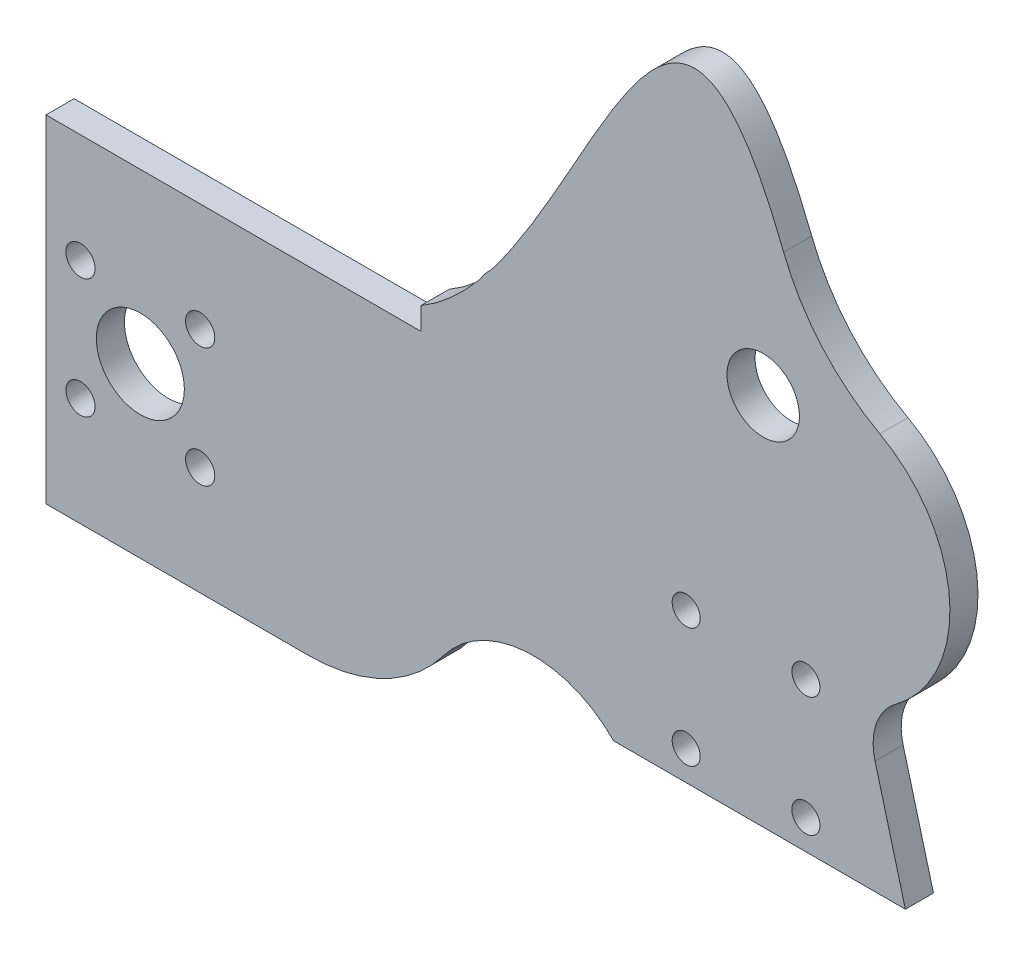
SolidWorks part; units mm, degrees
ref_plane "Front Plane" through (0, 0, 0) normal (0, 0, 1) x (1, 0, 0)
ref_plane "Top Plane" through (0, 0, 0) normal (0, 1, 0) x (1, 0, 0)
ref_plane "Right Plane" through (0, 0, 0) normal (1, 0, 0) x (0, 0, -1)
sketch "Sketch1" plane through (0, 0, 0) normal (0, 0, 1) x (1, 0, 0)
  line L0 (0, 0) -> (107.95, 0)
  line L3 (0, 38.1) -> (0, 25.4)
  line L4 (95.3675, 55.88) -> (0, 38.1)
  line L5 (0, 19.05) -> (100.2273, 19.05) construction
  line L6 (19.05, 19.05) -> (19.05, 28.62) construction
  line L7 (19.05, 19.05) -> (25.817, 25.817) construction
  line L8 (107.95, 0) -> (100.9363, 26.1756)
  line L10 (0, 12.7) -> (0, 0)
  line L11 (0, 25.4) -> (-7.62, 25.4)
  line L13 (0, 12.7) -> (-7.62, 12.7)
  line L14 (-7.62, 25.4) -> (-7.62, 12.7)
  line L15 (100.9363, 26.1756) -> (100.8688, 26.4276)
  arc A0 (100.8688, 26.4276) -> (95.3675, 55.88) centre (95.3675, 40.64) ccw
  circle A1 centre (95.3675, 40.64) radius 4.0957 construction
  circle A2 centre (19.05, 19.05) radius 9.57 construction
  circle A3 centre (25.817, 25.817) radius 1.651
  circle A4 centre (25.817, 12.283) radius 1.651
  circle A7 centre (12.283, 12.283) radius 1.651 [skipped]
  circle A8 centre (12.283, 25.817) radius 1.651 [skipped]
  point P26 (19.05, 19.05)
  dimension "D1" = 8.1915
  dimension "D5" = 15.24
  dimension "D4" = 19.14
  dimension "D7" = 3.302
  dimension "D11" = 97.0107
  dimension "D2" = 38.1
  dimension "D3" = 40.64
  dimension "D6" = 107.95
  dimension "D8" = 45
  dimension "D9" = 4
  dimension "D10" = 19.05
  dimension "D12" = 75
  dimension "D14" = 12.7
  dimension "D15" = 12.7
  dimension "D16" = 7.62
extrude "Boss-Extrude1" add sketch "Sketch1" along normal blind 3.175
sketch "Sketch2" plane through (0, 0, 3.175) normal (0, 0, 1) x (1, 0, 0)
  circle A0 centre (95.3675, 40.64) radius 38.1 construction
sketch "Sketch6" plane through (0, 0, 3.175) normal (0, 0, 1) x (1, 0, 0)
  line L0 (0, 0) -> (107.95, 0) construction
  line L1 (50.8, 0) -> (76.2, 0)
  arc A0 (76.2, 0) -> (50.8, 0) centre (63.5, 0) ccw
  dimension "D1" = 25.4
  dimension "D2" = 31.75
extrude "Cut-Extrude2" cut sketch "Sketch6" against normal blind 6.35
sketch "Sketch7" plane through (0, 0, 3.175) normal (0, 0, 1) x (1, 0, 0)
  line L0 (12.283, 25.817) -> (25.817, 12.283) construction
  line L1 (12.283, 12.283) -> (25.817, 25.817) construction
  circle A0 centre (19.05, 19.05) radius 4.9784
  circle A2 centre (80.7829, 12.2536) radius 1.5875
  circle A3 centre (94.316, 12.2536) radius 1.5875
  circle A4 centre (80.7829, 25.7876) radius 1.5875
  circle A5 centre (94.316, 25.7876) radius 1.5875
  dimension "D1" = 9.9568
extrude "Cut-Extrude3" cut sketch "Sketch7" against normal through all
fillet "Fillet1" radius 6.35 1 edges at (100.8688, 26.4276, 1.5875)
sketch "Sketch8" plane through (0, 0, 3.175) normal (0, 0, 1) x (1, 0, 0)
  line L1 (0, 38.1) -> (50.8, 38.1)
  line L2 (0, 38.1) -> (0, 50.8)
  line L3 (0, 50.8) -> (50.8, 50.8)
  line L4 (50.8, 38.1) -> (50.8, 50.8)
  dimension "D1" = 50.8
  dimension "D2" = 12.7
extrude "Cut-Extrude4" cut sketch "Sketch8" against normal blind 50.8
sketch "Sketch9" plane through (0, 0, 3.175) normal (0, 0, 1) x (1, 0, 0)
  line L3 (50.8, 40.64) -> (57.15, 40.64)
  line L5 (57.15, 40.64) -> (50.8, 40.64)
  line L6 (57.15, 40.64) -> (57.15, 50.8)
  line L7 (57.15, 50.8) -> (50.8, 50.8)
  line L8 (50.8, 40.64) -> (50.8, 50.8)
  line L9 (0, 38.1) -> (50.8, 38.1) construction
  line M8 (50.8, 47.571) -> (50.8, 38.1)
  line M21 (95.3675, 55.88) -> (50.8, 47.571)
  dimension "D1" = 10.16
  dimension "D2" = 2.54
  dimension "D3" = 6.35
extrude "Cut-Extrude5" cut sketch "Sketch9" against normal blind 19.304 contours L3 L6 M21 M8 region at (54.0583, 44.4092, 3.175)
fillet "Fillet6" radius 6.35 1 edges at (57.15, 40.64, 1.5875)
fillet "Fillet7" radius 6.35 1 edges at (57.15, 48.7549, 1.5875)
fillet "Fillet8" radius 19.05 1 edges at (50.8, 0, 1.5875)
sketch "Sketch12" plane through (0, 0, 3.175) normal (0, 0, 1) x (1, 0, 0)
  line L0 (107.95, 0) -> (146.812, 0) construction
  line L1 (8.0257, 45.4128) -> (80.6683, 75.7903) construction
  line L2 (95.3675, 40.64) -> (80.6683, 75.7903) construction
  line L3 (80.6683, 75.7903) -> (79.4434, 78.7195) construction
  line L4 (50.8, 40.64) -> (85.0271, 40.64)
  line L5 (85.0271, 40.64) -> (95.3675, 55.88)
  arc A0 (61.8128, 49.6242) -> (56.8883, 45.1859) centre (62.9766, 43.3817) ccw construction
  circle A1 centre (19.05, 19.05) radius 28.575 construction
  circle A2 centre (95.3675, 40.64) radius 38.1 construction
  circle A3 centre (80.6683, 75.7903) radius 3.175 construction
  spline S0 degree 3 poles (50.8, 40.64) (70.7778, 52.1788) (78.5943, 111.5434) (95.3675, 55.88) knots 0 0 0 0 1 1 1 1
  dimension "D2" = 6.35
  dimension "D1" = 38.862
extrude "Boss-Extrude2" add sketch "Sketch12" against normal blind 3.175
fillet "Fillet9" radius 24.13 1 edges at (95.3675, 55.88, 1.5875)
sketch "Sketch13" plane through (0, 38.1, 0) normal (0, 1, 0) x (1, 0, 0)
  line L0 (8.382, -3.175) -> (8.382, 0)
  line L1 (0, -3.175) -> (50.8, -3.175) construction
  line L2 (0, 0) -> (50.8, 0) construction
  line L3 (0, -3.175) -> (0, 0) construction
  dimension "D1" = 8.382
extrude "Cut-Extrude6" cut sketch "Sketch13" against normal through all
sketch "Sketch14" plane through (0, 0, 3.175) normal (0, 0, 1) x (1, 0, 0)
  circle A0 centre (89.49, 51.1876) radius 4.0958
  circle A1 centre (94.316, 25.7876) radius 1.5875 construction
  circle A2 centre (95.3675, 40.64) radius 4.0957 construction
  dimension "D1" = 4.826
  dimension "D2" = 25.4
extrude "Cut-Extrude7" cut sketch "Sketch14" against normal through all
sketch "Sketch17" plane through (0, 0, 3.175) normal (0, 0, 1) x (1, 0, 0)
  line L0 (76.2, 0) -> (107.95, 0) construction
  line L1 (64.0585, 8.89) -> (108.994, 8.89)
  line L2 (64.0585, 8.89) -> (64.0585, 0)
  line L3 (64.0585, 0) -> (108.994, 0)
  line L4 (108.994, 8.89) -> (108.994, 0)
  dimension "D1" = 8.89
extrude "Cut-Extrude10" cut sketch "Sketch17" against normal through all
sketch "Sketch18" plane through (0, 0, 3.175) normal (0, 0, 1) x (1, 0, 0)
  line L0 (19.05, 14.0716) -> (19.05, 24.0284) construction
  circle A0 centre (19.05, 19.05) radius 4.9784 construction
  circle A1 centre (25.817, 25.817) radius 1.651 construction
  circle A2 centre (25.817, 12.283) radius 1.651 construction
  circle A3 centre (12.283, 12.283) radius 1.651
  circle A4 centre (12.283, 25.817) radius 1.651
extrude "Cut-Extrude11" cut sketch "Sketch18" against normal through all
